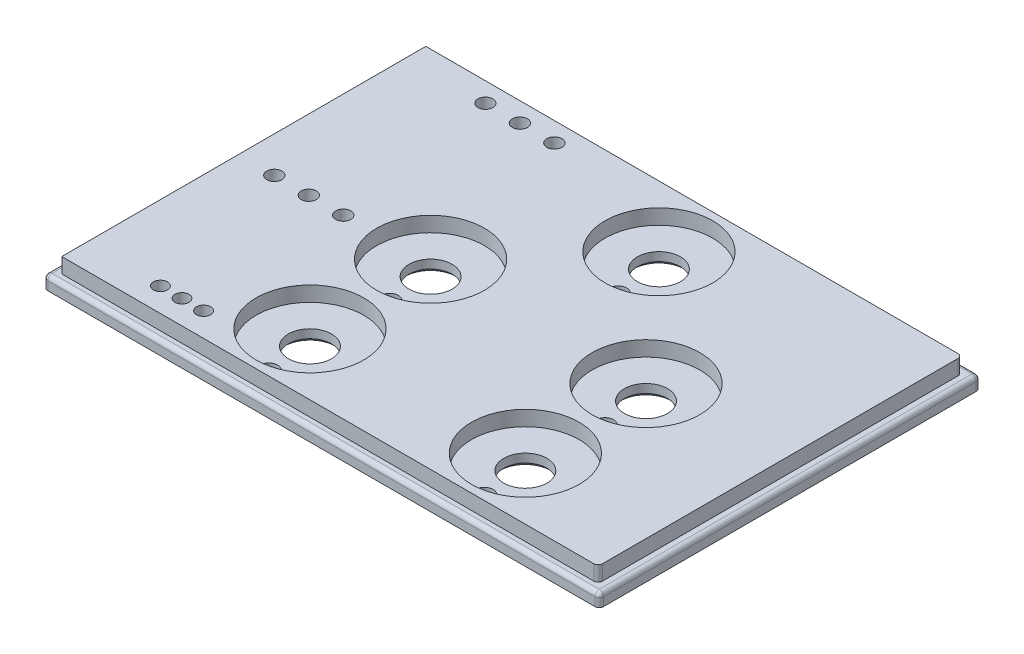
SolidWorks part; units mm, degrees
ref_plane "Спереди" through (0, 0, 0) normal (0, 0, 1) x (1, 0, 0)
ref_plane "Сверху" through (0, 0, 0) normal (0, 1, 0) x (1, 0, 0)
ref_plane "Справа" through (0, 0, 0) normal (1, 0, 0) x (0, 0, -1)
sketch "Эскиз1" plane through (0, 37.5, 0) normal (0, 1, 0) x (1, 0, 0)
  line L1 (127, -2) -> (127, 87) construction
  line L2 (-2, 87) -> (0, 87) construction
  line L3 (127, -2) -> (127, 87) construction
  line L4 (127, -2) -> (0, -2) construction
  line L5 (127, -2) -> (-2, -2) construction
  line L6 (-2, 87) -> (-2, -2) construction
  line L7 (-2, 87) -> (-2, -2) construction
  line L8 (62.5, 87) -> (62.5, -2) construction
  line L9 (-2, 87) -> (0, 87) construction
  line L10 (-2, 86.75) -> (127, 86.75)
  line L11 (-2, 86.75) -> (-2, -1.75)
  line L12 (-2, -1.75) -> (127, -1.75)
  line L13 (127, 86.75) -> (127, -1.75)
  line L14 (-2, 86.75) -> (127, -1.75) construction
  line L15 (-2, -1.75) -> (127, 86.75) construction
  point P8 (62.5, 42.5)
  dimension "D1" = 0.25
  dimension "D2" = 0.25
extrude "Бобышка-Вытянуть1" add sketch "Эскиз1" along normal blind 3
sketch "Эскиз2" plane through (0, 40.5, 0) normal (0, 1, 0) x (1, 0, 0)
  circle A0 centre (43.6, 14.5) radius 5 construction
  circle A1 centre (43.6, 14.5) radius 5 construction
  circle A3 centre (43.6, 42.5) radius 5 construction
  circle A4 centre (68.6, 70.5) radius 5 construction
  circle A5 centre (68.6, 70.5) radius 5 construction
  circle A6 centre (43.6, 42.5) radius 5 construction
  circle A7 centre (93.6, 42.5) radius 5 construction
  circle A8 centre (93.6, 42.5) radius 5 construction
  circle A9 centre (93.6, 14.5) radius 5 construction
  circle A10 centre (93.6, 14.5) radius 5 construction
  circle A11 centre (43.6, 14.5) radius 5
  circle A12 centre (43.6, 42.5) radius 5
  circle A13 centre (68.6, 70.5) radius 5
  circle A14 centre (93.6, 42.5) radius 5
  circle A15 centre (93.6, 14.5) radius 5
  dimension "D1" = 0
extrude "Вырез-Вытянуть1" cut sketch "Эскиз2" against normal through all
sketch "Эскиз3" plane through (0, 40.5, 0) normal (0, 1, 0) x (1, 0, 0)
  circle A0 centre (34.5998, 80.2301) radius 1.75
  circle A1 centre (27.5999, 5.8) radius 1.5
  circle A2 centre (27.5999, 5.8) radius 1.5 construction
  circle A3 centre (22.5999, 5.8) radius 1.5
  circle A4 centre (22.5999, 5.8) radius 1.5 construction
  circle A5 centre (17.5999, 5.8) radius 1.5
  circle A6 centre (17.5999, 5.8) radius 1.5 construction
  circle A7 centre (34.5998, 80.2301) radius 1.5
  circle A8 centre (34.5998, 80.2301) radius 1.5 construction
  circle A9 centre (26.6, 80.2299) radius 1.5
  circle A10 centre (26.6, 80.2299) radius 1.5 construction
  circle A11 centre (18.5998, 80.2301) radius 1.5
  circle A12 centre (18.5998, 80.2301) radius 1.5 construction
  circle A13 centre (8.5998, 41.2301) radius 1.5
  circle A14 centre (8.5998, 41.2301) radius 1.5 construction
  circle A15 centre (16.5998, 41.2301) radius 1.5
  circle A16 centre (16.5998, 41.2301) radius 1.5 construction
  circle A17 centre (24.6, 41.2299) radius 1.5
  circle A18 centre (24.6, 41.2299) radius 1.5 construction
  circle A19 centre (26.6, 80.2299) radius 1.75
  circle A20 centre (18.5998, 80.2301) radius 1.75
  circle A21 centre (8.5998, 41.2301) radius 1.75
  circle A22 centre (16.5998, 41.2301) radius 1.75
  circle A23 centre (24.6, 41.2299) radius 1.75
  circle A24 centre (27.5999, 5.8) radius 1.625
  circle A25 centre (22.5999, 5.8) radius 1.625
  circle A26 centre (17.5999, 5.8) radius 1.625
  dimension "D10" = 3.5
  dimension "D11" = 3.25
  dimension "D1" = 0
  dimension "D2" = 0
  dimension "D3" = 0
  dimension "D4" = 0
  dimension "D5" = 0
  dimension "D6" = 0
  dimension "D7" = 0
  dimension "D8" = 0
  dimension "D9" = 0
extrude "Вырез-Вытянуть2" cut sketch "Эскиз3" against normal through all
chamfer "Фаска1" distance 1 angle 45 5 edges at (93.6, 37.5, -9.5) (93.6, 37.5, -37.5) (68.6, 37.5, -65.5) (43.6, 37.5, -37.5) (43.6, 37.5, -9.5)
chamfer "Фаска2" distance 1 angle 45 6 edges at (34.5998, 37.5, -78.4801) (26.6, 37.5, -78.4799) (18.5998, 37.5, -78.4801) (24.6, 37.5, -39.4799) (16.5998, 37.5, -39.4801) (8.5998, 37.5, -39.4801)
sketch "Эскиз6" plane through (0, 40.5, 0) normal (0, 1, 0) x (1, 0, 0)
  line L0 (125, 0) -> (0, 0) construction
  line L1 (125, 0) -> (125, 85) construction
  line L2 (125, 0) -> (0, 0) construction
  line L3 (125, 0) -> (125, 85) construction
  line L4 (0, -4) -> (0, 89) construction
  line L5 (0, -4) -> (0, 89) construction
  line L6 (125, 85) -> (0, 85) construction
  line L7 (125, 85) -> (0, 85) construction
  line L8 (62.5, 85) -> (62.5, 0) construction
  line L10 (124.75, 0.25) -> (0.25, 0.25)
  line L11 (124.75, 0.25) -> (124.75, 84.75)
  line L12 (124.75, 84.75) -> (0.25, 84.75)
  line L13 (0.25, 0.25) -> (0.25, 84.75)
  line L14 (124.75, 0.25) -> (0.25, 84.75) construction
  line L15 (124.75, 84.75) -> (0.25, 0.25) construction
  point P8 (62.5, 42.5)
  dimension "D1" = 0.25
  dimension "D2" = 0.25
extrude "Бобышка-Вытянуть3" add sketch "Эскиз6" along normal blind 3.5
sketch "Эскиз7" plane through (0, 40.5, 0) normal (0, -1, 0) x (1, 0, 0)
  circle A0 centre (26.6, -80.2299) radius 1.75 construction
  circle A1 centre (43.6, -42.5) radius 5
  circle A2 centre (43.6, -42.5) radius 5
  circle A3 centre (43.6, -14.5) radius 5
  circle A4 centre (43.6, -14.5) radius 5
  circle A5 centre (93.6, -14.5) radius 5
  circle A6 centre (93.6, -14.5) radius 5
  circle A7 centre (93.6, -42.5) radius 5
  circle A8 centre (93.6, -42.5) radius 5
  circle A9 centre (68.6, -70.5) radius 5
  circle A10 centre (68.6, -70.5) radius 5
  circle A11 centre (24.6, -41.2299) radius 1.75
  circle A12 centre (24.6, -41.2299) radius 1.75
  circle A13 centre (16.5998, -41.2301) radius 1.75
  circle A14 centre (16.5998, -41.2301) radius 1.75
  circle A15 centre (8.5998, -41.2301) radius 1.75
  circle A16 centre (8.5998, -41.2301) radius 1.75
  circle A17 centre (18.5998, -80.2301) radius 1.75
  circle A18 centre (18.5998, -80.2301) radius 1.75
  circle A19 centre (26.6, -80.2299) radius 1.75
  circle A21 centre (34.5998, -80.2301) radius 1.75
  circle A22 centre (34.5998, -80.2301) radius 1.75
  circle A25 centre (22.5999, -5.8) radius 1.625 construction
  circle A26 centre (22.5999, -5.8) radius 1.625
  circle A27 centre (17.5999, -5.8) radius 1.625 construction
  circle A28 centre (27.5999, -5.8) radius 1.625 construction
  circle A29 centre (27.5999, -5.8) radius 1.625
  circle A30 centre (17.5999, -5.8) radius 1.625
  dimension "D1" = 0
  dimension "D2" = 0
  dimension "D3" = 0
  dimension "D4" = 0
  dimension "D5" = 0
  dimension "D6" = 0
  dimension "D7" = 0
  dimension "D8" = 0
  dimension "D9" = 0
  dimension "D10" = 0
extrude "Вырез-Вытянуть3" cut sketch "Эскиз7" against normal through all
sketch "Эскиз9" plane through (0, 44, 0) normal (0, 1, 0) x (1, 0, 0)
  circle A0 centre (43.6, 14.5) radius 12.5
  circle A1 centre (43.6, 42.5) radius 12.5
  circle A2 centre (68.6, 70.5) radius 12.5
  circle A3 centre (93.6, 42.5) radius 12.5
  circle A4 centre (93.6, 14.5) radius 12.5
  dimension "D1" = 25
extrude "Вырез-Вытянуть4" cut sketch "Эскиз9" against normal blind 3.5
fillet "Скругление4" radius 1 4 edges at (127, 39, 1.75) (124.75, 42.25, -0.25) (124.75, 42.25, -84.75) (127, 39, -86.75)
fillet "Скругление5" radius 1 5 edges at (62, 40.5, 1.75) (126.7071, 40.5, 1.4571) (127, 40.5, -42.5) (126.7071, 40.5, -86.4571) (62, 40.5, -86.75)
fillet "Скругление6" radius 1 5 edges at (-2, 38.5, 1.75) (-2, 40.2071, 1.4571) (-2, 40.5, -42.5) (-2, 40.2071, -86.4571) (-2, 38.5, -86.75)
sketch "Эскиз10" plane through (0, 44, 0) normal (0, 1, 0) x (1, 0, 0)
  circle A0 centre (93.6, 33) radius 1.5 construction
  circle A1 centre (93.6, 33) radius 1.5 construction
  circle A2 centre (93.6, 5) radius 1.5 construction
  circle A3 centre (93.6, 5) radius 1.5 construction
  circle A4 centre (43.6, 5) radius 1.5 construction
  circle A5 centre (43.6, 5) radius 1.5 construction
  circle A6 centre (43.6, 33) radius 1.5 construction
  circle A7 centre (43.6, 33) radius 1.5 construction
  circle A8 centre (68.6, 61.0001) radius 1.5 construction
  circle A9 centre (68.6, 61.0001) radius 1.5 construction
  circle A10 centre (43.6, 5) radius 2
  circle A11 centre (43.6, 33) radius 2
  circle A12 centre (68.6, 61.0001) radius 2
  circle A13 centre (93.6, 33) radius 2
  circle A14 centre (93.6, 5) radius 2
  dimension "D1" = 0.5
sketch "Эскиз11" plane through (0, 37.5, 0) normal (0, -1, 0) x (1, 0, 0)
  circle A0 centre (43.6, -5) radius 2 construction
  circle A1 centre (43.6, -33) radius 2 construction
  circle A2 centre (93.6, -5) radius 2 construction
  circle A3 centre (93.6, -33) radius 2 construction
  circle A4 centre (68.6, -61.0001) radius 2 construction
  circle A5 centre (43.6, -5) radius 2
  circle A6 centre (43.6, -33) radius 2
  circle A7 centre (93.6, -5) radius 2
  circle A8 centre (93.6, -33) radius 2
  circle A9 centre (68.6, -61.0001) radius 2
extrude "Вырез-Вытянуть5" cut sketch "Эскиз11" against normal up to surface (3 mm away) up to face at (93.6, 40.5, -2)
